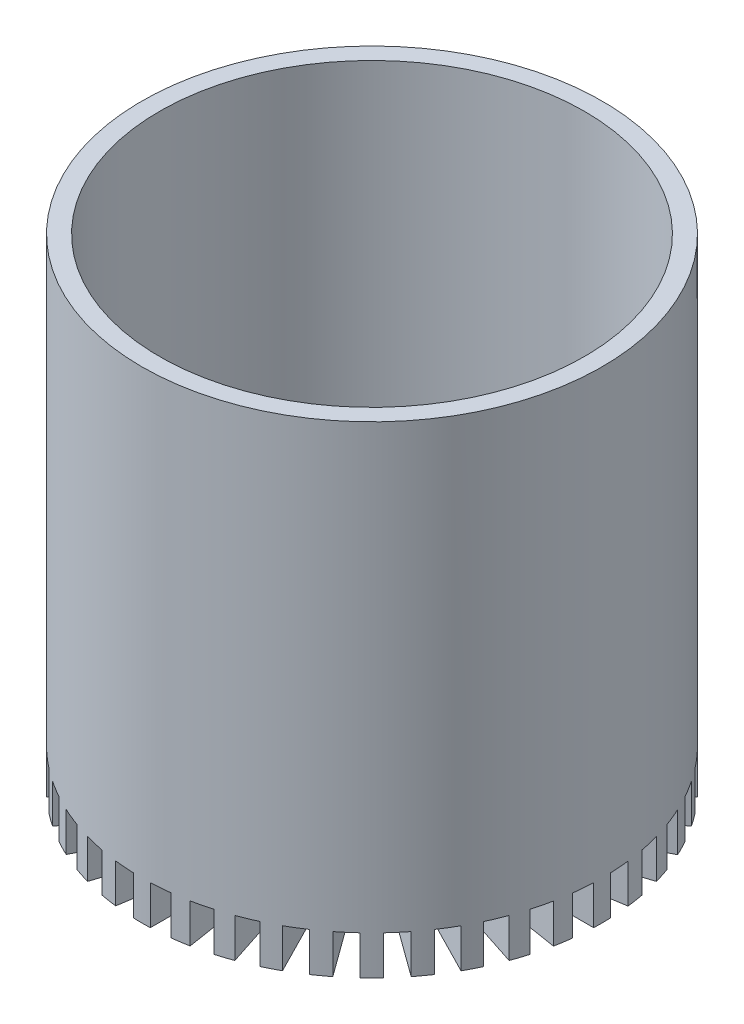
SolidWorks part; units mm, degrees
ref_plane "Front Plane" through (0, 0, 0) normal (0, 0, 1) x (1, 0, 0)
ref_plane "Top Plane" through (0, 0, 0) normal (0, 1, 0) x (1, 0, 0)
ref_plane "Right Plane" through (0, 0, 0) normal (1, 0, 0) x (0, 0, -1)
sketch "Sketch1" plane through (0, 0, 0) normal (0, 1, 0) x (1, 0, 0)
  circle A0 centre (0, 0) radius 38.1
  dimension "D1" = 76.2
extrude "Boss-Extrude1" add sketch "Sketch1" along normal blind 76.2
shell "Shell2" thickness 3.175 removed face at (0, 76.2, 38.1) outward yes
ref_axis "Axis1" through (0, 76.2, 0) along (0, -1, 0)
sketch "Sketch2" plane through (0, -3.175, 0) normal (0, -1, 0) x (-1, 0, 0)
  line L0 (0, 0) -> (0, 41.275)
  line L1 (-1.5, -41.275) -> (-1.5, 41.275)
  line L2 (-1.5, -41.275) -> (1.5, -41.275)
  line L3 (-1.5, 41.275) -> (1.5, 41.275)
  line L4 (1.5, -41.275) -> (1.5, 41.275)
  line L5 (-1.5, -41.275) -> (1.5, 41.275) construction
  line L6 (-1.5, 41.275) -> (1.5, -41.275) construction
  line L7 (-23.0473, -34.2739) -> (25.4744, 32.5105)
  line L8 (-25.4744, -32.5105) -> (23.0473, 34.2739)
  line L9 (-25.4744, -32.5105) -> (-23.0473, -34.2739)
  line L10 (23.0473, 34.2739) -> (25.4744, 32.5105)
  line L11 (-38.7913, -14.1813) -> (39.7184, 11.3281)
  line L12 (-39.7184, -11.3281) -> (38.7913, 14.1813)
  line L13 (-39.7184, -11.3281) -> (-38.7913, -14.1813)
  line L14 (38.7913, 14.1813) -> (39.7184, 11.3281)
  line L15 (-39.7184, 11.3281) -> (38.7913, -14.1813)
  line L16 (-38.7913, 14.1813) -> (39.7184, -11.3281)
  line L17 (-38.7913, 14.1813) -> (-39.7184, 11.3281)
  line L18 (39.7184, -11.3281) -> (38.7913, -14.1813)
  line L19 (-25.4744, 32.5105) -> (23.0473, -34.2739)
  line L20 (-23.0473, 34.2739) -> (25.4744, -32.5105)
  line L21 (-23.0473, 34.2739) -> (-25.4744, 32.5105)
  line L22 (25.4744, -32.5105) -> (23.0473, -34.2739)
  line L23 (-1.5, 41.275) -> (-1.5, -41.275)
  line L24 (1.5, 41.275) -> (1.5, -41.275)
  line L25 (1.5, 41.275) -> (-1.5, 41.275)
  line L26 (1.5, -41.275) -> (-1.5, -41.275)
  line L27 (-14.1813, 38.7913) -> (11.3281, -39.7184)
  line L28 (14.1813, -38.7913) -> (11.3281, -39.7184)
  line L29 (-11.3281, 39.7184) -> (14.1813, -38.7913)
  line L30 (-11.3281, 39.7184) -> (-14.1813, 38.7913)
  line L31 (11.3281, 39.7184) -> (-14.1813, -38.7913)
  line L32 (-11.3281, -39.7184) -> (-14.1813, -38.7913)
  line L33 (14.1813, 38.7913) -> (-11.3281, -39.7184)
  line L34 (14.1813, 38.7913) -> (11.3281, 39.7184)
  line L35 (32.5105, 25.4744) -> (-34.2739, -23.0473)
  line L36 (-32.5105, -25.4744) -> (-34.2739, -23.0473)
  line L37 (34.2739, 23.0473) -> (-32.5105, -25.4744)
  line L38 (34.2739, 23.0473) -> (32.5105, 25.4744)
  line L39 (-41.275, 1.5) -> (41.275, 1.5)
  line L40 (-41.275, 1.5) -> (-41.275, -1.5)
  line L41 (-41.275, -1.5) -> (41.275, -1.5)
  line L42 (41.275, 1.5) -> (41.275, -1.5)
  line L43 (-34.2739, 23.0473) -> (32.5105, -25.4744)
  line L44 (34.2739, -23.0473) -> (32.5105, -25.4744)
  line L45 (-32.5105, 25.4744) -> (34.2739, -23.0473)
  line L46 (-32.5105, 25.4744) -> (-34.2739, 23.0473)
  line L47 (38.7913, 14.1813) -> (-39.7184, -11.3281)
  line L48 (-38.7913, -14.1813) -> (-39.7184, -11.3281)
  line L49 (39.7184, 11.3281) -> (-38.7913, -14.1813)
  line L50 (39.7184, 11.3281) -> (38.7913, 14.1813)
  line L51 (39.7184, -11.3281) -> (-38.7913, 14.1813)
  line L52 (-39.7184, 11.3281) -> (-38.7913, 14.1813)
  line L53 (38.7913, -14.1813) -> (-39.7184, 11.3281)
  line L54 (38.7913, -14.1813) -> (39.7184, -11.3281)
  line L55 (25.4744, -32.5105) -> (-23.0473, 34.2739)
  line L56 (-25.4744, 32.5105) -> (-23.0473, 34.2739)
  line L57 (23.0473, -34.2739) -> (-25.4744, 32.5105)
  line L58 (23.0473, -34.2739) -> (25.4744, -32.5105)
  line L59 (1.5, 41.275) -> (1.5, -41.275)
  line L60 (1.5, 41.275) -> (-1.5, 41.275)
  line L61 (-1.5, 41.275) -> (-1.5, -41.275)
  line L62 (1.5, -41.275) -> (-1.5, -41.275)
  line L63 (23.0473, 34.2739) -> (-25.4744, -32.5105)
  line L64 (-23.0473, -34.2739) -> (-25.4744, -32.5105)
  line L65 (25.4744, 32.5105) -> (-23.0473, -34.2739)
  line L66 (25.4744, 32.5105) -> (23.0473, 34.2739)
  line L67 (14.1813, -38.7913) -> (-11.3281, 39.7184)
  line L68 (-14.1813, 38.7913) -> (-11.3281, 39.7184)
  line L69 (11.3281, -39.7184) -> (-14.1813, 38.7913)
  line L70 (11.3281, -39.7184) -> (14.1813, -38.7913)
  line L71 (-11.3281, -39.7184) -> (14.1813, 38.7913)
  line L72 (11.3281, 39.7184) -> (14.1813, 38.7913)
  line L73 (-14.1813, -38.7913) -> (11.3281, 39.7184)
  line L74 (-14.1813, -38.7913) -> (-11.3281, -39.7184)
  line L75 (-32.5105, -25.4744) -> (34.2739, 23.0473)
  line L76 (32.5105, 25.4744) -> (34.2739, 23.0473)
  line L77 (-34.2739, -23.0473) -> (32.5105, 25.4744)
  line L78 (-34.2739, -23.0473) -> (-32.5105, -25.4744)
  line L79 (41.275, -1.5) -> (-41.275, -1.5)
  line L80 (41.275, -1.5) -> (41.275, 1.5)
  line L81 (41.275, 1.5) -> (-41.275, 1.5)
  line L82 (-41.275, -1.5) -> (-41.275, 1.5)
  line L83 (34.2739, -23.0473) -> (-32.5105, 25.4744)
  line L84 (-34.2739, 23.0473) -> (-32.5105, 25.4744)
  line L85 (32.5105, -25.4744) -> (-34.2739, 23.0473)
  line L86 (32.5105, -25.4744) -> (34.2739, -23.0473)
  line L87 (0, 0) -> (6.4277, 40.7714)
  line L88 (-7.9094, -40.5378) -> (4.946, 41.005)
  line L89 (-7.9094, -40.5378) -> (-4.946, -41.005)
  line L90 (4.946, 41.005) -> (7.9094, 40.5378)
  line L91 (-4.946, -41.005) -> (7.9094, 40.5378)
  line L92 (-28.1035, -30.2666) -> (30.2264, 28.1468)
  line L93 (-30.2264, -28.1468) -> (28.1035, 30.2666)
  line L94 (-30.2264, -28.1468) -> (-28.1035, -30.2666)
  line L95 (28.1035, 30.2666) -> (30.2264, 28.1468)
  line L96 (-40.5265, -7.9673) -> (40.9979, 5.0046)
  line L97 (-40.9979, -5.0046) -> (40.5265, 7.9673)
  line L98 (-40.9979, -5.0046) -> (-40.5265, -7.9673)
  line L99 (40.5265, 7.9673) -> (40.9979, 5.0046)
  line L100 (-37.4697, 17.3752) -> (36.1096, -20.0492)
  line L101 (-36.1096, 20.0492) -> (37.4697, -17.3752)
  line L102 (-36.1096, 20.0492) -> (-37.4697, 17.3752)
  line L103 (37.4697, -17.3752) -> (36.1096, -20.0492)
  line L104 (-20.1008, 36.081) -> (17.4287, -37.4448)
  line L105 (-17.4287, 37.4448) -> (20.1008, -36.081)
  line L106 (-17.4287, 37.4448) -> (-20.1008, 36.081)
  line L107 (20.1008, -36.081) -> (17.4287, -37.4448)
  line L108 (4.946, 41.005) -> (-7.9094, -40.5378)
  line L109 (7.9094, 40.5378) -> (-4.946, -41.005)
  line L110 (7.9094, 40.5378) -> (4.946, 41.005)
  line L111 (-4.946, -41.005) -> (-7.9094, -40.5378)
  line L112 (-7.9673, 40.5265) -> (5.0046, -40.9979)
  line L113 (7.9673, -40.5265) -> (5.0046, -40.9979)
  line L114 (-5.0046, 40.9979) -> (7.9673, -40.5265)
  line L115 (-5.0046, 40.9979) -> (-7.9673, 40.5265)
  line L116 (17.3752, 37.4697) -> (-20.0492, -36.1096)
  line L117 (-17.3752, -37.4697) -> (-20.0492, -36.1096)
  line L118 (20.0492, 36.1096) -> (-17.3752, -37.4697)
  line L119 (20.0492, 36.1096) -> (17.3752, 37.4697)
  line L120 (36.081, 20.1008) -> (-37.4448, -17.4287)
  line L121 (-36.081, -20.1008) -> (-37.4448, -17.4287)
  line L122 (37.4448, 17.4287) -> (-36.081, -20.1008)
  line L123 (37.4448, 17.4287) -> (36.081, 20.1008)
  line L124 (-40.5378, 7.9094) -> (41.005, -4.946)
  line L125 (-40.5378, 7.9094) -> (-41.005, 4.946)
  line L126 (-41.005, 4.946) -> (40.5378, -7.9094)
  line L127 (41.005, -4.946) -> (40.5378, -7.9094)
  line L128 (-30.2666, 28.1035) -> (28.1468, -30.2264)
  line L129 (30.2666, -28.1035) -> (28.1468, -30.2264)
  line L130 (-28.1468, 30.2264) -> (30.2666, -28.1035)
  line L131 (-28.1468, 30.2264) -> (-30.2666, 28.1035)
  line L132 (40.5265, 7.9673) -> (-40.9979, -5.0046)
  line L133 (-40.5265, -7.9673) -> (-40.9979, -5.0046)
  line L134 (40.9979, 5.0046) -> (-40.5265, -7.9673)
  line L135 (40.9979, 5.0046) -> (40.5265, 7.9673)
  line L136 (37.4697, -17.3752) -> (-36.1096, 20.0492)
  line L137 (-37.4697, 17.3752) -> (-36.1096, 20.0492)
  line L138 (36.1096, -20.0492) -> (-37.4697, 17.3752)
  line L139 (36.1096, -20.0492) -> (37.4697, -17.3752)
  line L140 (20.1008, -36.081) -> (-17.4287, 37.4448)
  line L141 (-20.1008, 36.081) -> (-17.4287, 37.4448)
  line L142 (17.4287, -37.4448) -> (-20.1008, 36.081)
  line L143 (17.4287, -37.4448) -> (20.1008, -36.081)
  line L144 (7.9094, 40.5378) -> (-4.946, -41.005)
  line L145 (7.9094, 40.5378) -> (4.946, 41.005)
  line L146 (4.946, 41.005) -> (-7.9094, -40.5378)
  line L147 (-4.946, -41.005) -> (-7.9094, -40.5378)
  line L148 (28.1035, 30.2666) -> (-30.2264, -28.1468)
  line L149 (-28.1035, -30.2666) -> (-30.2264, -28.1468)
  line L150 (30.2264, 28.1468) -> (-28.1035, -30.2666)
  line L151 (30.2264, 28.1468) -> (28.1035, 30.2666)
  line L152 (7.9673, -40.5265) -> (-5.0046, 40.9979)
  line L153 (-7.9673, 40.5265) -> (-5.0046, 40.9979)
  line L154 (5.0046, -40.9979) -> (-7.9673, 40.5265)
  line L155 (5.0046, -40.9979) -> (7.9673, -40.5265)
  line L156 (-17.3752, -37.4697) -> (20.0492, 36.1096)
  line L157 (17.3752, 37.4697) -> (20.0492, 36.1096)
  line L158 (-20.0492, -36.1096) -> (17.3752, 37.4697)
  line L159 (-20.0492, -36.1096) -> (-17.3752, -37.4697)
  line L160 (-36.081, -20.1008) -> (37.4448, 17.4287)
  line L161 (36.081, 20.1008) -> (37.4448, 17.4287)
  line L162 (-37.4448, -17.4287) -> (36.081, 20.1008)
  line L163 (-37.4448, -17.4287) -> (-36.081, -20.1008)
  line L164 (40.5378, -7.9094) -> (-41.005, 4.946)
  line L165 (40.5378, -7.9094) -> (41.005, -4.946)
  line L166 (41.005, -4.946) -> (-40.5378, 7.9094)
  line L167 (-41.005, 4.946) -> (-40.5378, 7.9094)
  line L168 (30.2666, -28.1035) -> (-28.1468, 30.2264)
  line L169 (-30.2666, 28.1035) -> (-28.1468, 30.2264)
  line L170 (28.1468, -30.2264) -> (-30.2666, 28.1035)
  line L171 (28.1468, -30.2264) -> (30.2666, -28.1035)
  line L172 (-7.9094, -40.5378) -> (7.9094, 40.5378) construction
  line L173 (4.946, 41.005) -> (-4.946, -41.005) construction
  circle A1 centre (0, 0) radius 41.275 construction
  circle A2 centre (0, 0) radius 41.275
  circle A3 centre (0, 0) radius 41.275
  dimension "D1" = 3
  dimension "D2" = 6
  dimension "D3" = 4
  dimension "D4" = 2
extrude "Boss-Extrude2" add sketch "Sketch2" along normal blind 7 contours L4 L3 L1 L2 | L7 L10 L8 L9 | L11 L14 L12 L13 | L15 L18 L16 L17 | L20 L22 L19 L21 | L35 L36 L37 L38 | L39 L42 L41 L40 | L43 L44 L45 L46 | L27 L28 L29 L30 | L31 L32 L33 L34 | L116 L117 L118 L119 | L92 L95 L93 L94 | L160 L161 L162 L163 | L96 L99 L97 L98 | L124 L127 L126 L125 | L136 L137 L138 L139 | L168 L169 L170 L171 | L104 L107 L105 L106 | L112 L113 L114 L115 | L144 L147 L146 L145
sketch "Sketch3" plane through (0, -3.175, 0) normal (0, -1, 0) x (1, 0, 0)
  circle A0 centre (0, 0) radius 41.275
  circle A1 centre (0, 0) radius 61.9063
extrude "Cut-Extrude1" cut sketch "Sketch3" against normal through all both and the other way through all
sketch "Sketch4" plane through (0, -10.175, 0) normal (0, -1, 0) x (1, 0, 0)
  circle A0 centre (0, 0) radius 20.64
extrude "Cut-Extrude2" cut sketch "Sketch4" against normal up to surface (7 mm away) up to face at (32.9158, -3.175, -7.8899)
scale "Scale1" scale about centroid uniform scaling yes scale factor 0.615385
